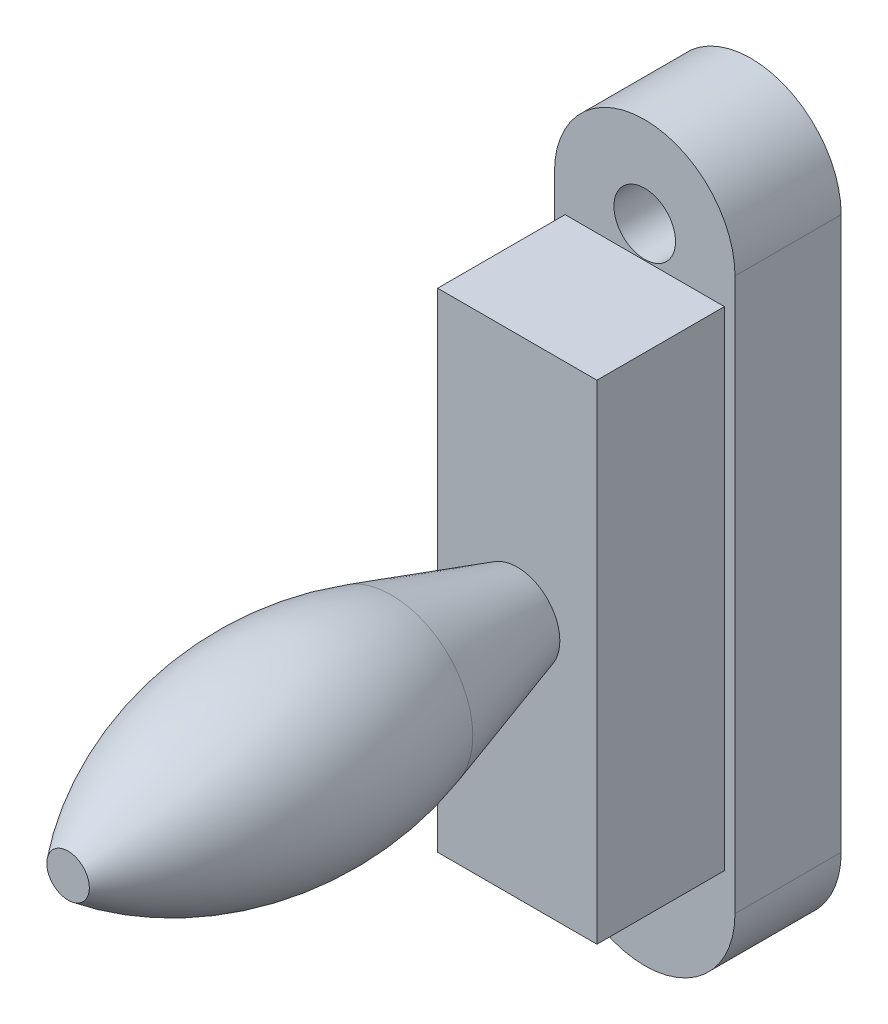
SolidWorks part; units mm, degrees
ref_plane "Front" through (0, 0, 0) normal (0, 0, 1) x (1, 0, 0)
ref_plane "Top" through (0, 0, 0) normal (0, 1, 0) x (1, 0, 0)
ref_plane "Right" through (0, 0, 0) normal (1, 0, 0) x (0, 0, -1)
sketch "Sketch1" plane through (0, 0, 0) normal (0, 0, 1) x (1, 0, 0)
  line L0 (0, 0) -> (0, 26) construction
  line L1 (-4.25, 0) -> (-4.25, 26)
  line L2 (4.25, 0) -> (4.25, 26)
  line L4 (-2.25, 3) -> (2.25, 3)
  line L5 (-2.25, 3) -> (-2.25, 23)
  line L6 (-2.25, 23) -> (2.25, 23)
  line L7 (2.25, 3) -> (2.25, 23)
  arc A0 (-4.25, 0) -> (4.25, 0) centre (0, 0) ccw
  arc A1 (4.25, 26) -> (-4.25, 26) centre (0, 26) ccw
  circle A2 centre (0, 26) radius 1.45
  circle A3 centre (0, 0) radius 1.45
  point P3 (0, 13)
  point P12 (0, 23)
  point P17 (4.25, 13)
  point P21 (2.25, 13)
  dimension "D1" = 2.9
  dimension "D2" = 26
  dimension "D3" = 4.5
  dimension "D4" = 2
  dimension "D5" = 20
extrude "Boss-Extrude1" add sketch "Sketch1" along normal blind 5
sketch "Sketch2" plane through (0, 0, 5) normal (0, 0, 1) x (1, 0, 0)
  line L0 (2.25, 23) -> (-2.25, 23) construction
  line L1 (2.25, 23) -> (-2.25, 23)
  line L2 (-2.25, 3) -> (2.25, 3) construction
  line L3 (2.25, 3) -> (2.25, 23) construction
  line L4 (-2.25, 23) -> (-2.25, 3) construction
  line L5 (-2.25, 3) -> (2.25, 3)
  line L6 (2.25, 3) -> (2.25, 23)
  line L7 (-2.25, 23) -> (-2.25, 3)
  line L8 (3.75, 1.5) -> (3.75, 24.5)
  line L9 (3.75, 24.5) -> (-3.75, 24.5)
  line L10 (-3.75, 24.5) -> (-3.75, 1.5)
  line L11 (-3.75, 1.5) -> (3.75, 1.5)
  dimension "D1" = 1.5
extrude "Boss-Extrude2" add sketch "Sketch2" along normal blind 5
sketch "Sketch3" plane through (0, 0, 10) normal (0, 0, 1) x (1, 0, 0)
  line L1 (-3.75, 24.5) -> (3.75, 24.5)
  line L2 (-3.75, 24.5) -> (-3.75, 1.5)
  line L3 (-3.75, 1.5) -> (3.75, 1.5)
  line L4 (3.75, 24.5) -> (3.75, 1.5)
extrude "Boss-Extrude3" add sketch "Sketch3" along normal blind 1
sketch "Sketch4" plane through (0, 0, 11) normal (0, 0, 1) x (1, 0, 0)
  line L1 (-3.75, 1.5) -> (3.75, 1.5) construction
  line L2 (-3.75, 1.5) -> (-3.75, 24.5) construction
  line L3 (-3.75, 24.5) -> (3.75, 24.5) construction
  line L4 (3.75, 1.5) -> (3.75, 24.5) construction
  line L5 (-3.75, 1.5) -> (3.75, 24.5) construction
  line L6 (-3.75, 24.5) -> (3.75, 1.5) construction
  point P0 (0, 13)
ref_axis "Axis1" through (0, 13, 11) along (0, 0, 1)
ref_plane "Plane1" through (0, 0, 0) normal (1, 0, 0) x (0, 0, -1)
sketch "Sketch5" plane through (0, 0, 0) normal (1, 0, 0) x (0, 0, -1)
  line L0 (-11, 13) -> (-11, 15.0039)
  line L1 (-11, 24.5) -> (-11, 1.5) construction
  line L2 (-11, 15.0039) -> (-16.9245, 16.8293)
  line L3 (-32.1512, 14.0019) -> (-32.1512, 13)
  line L4 (-32.1512, 13) -> (-11, 13)
  arc A0 (-16.9245, 16.8293) -> (-32.1512, 14.0019) centre (-21.8388, 0.8799) ccw
revolve "Revolve1" add sketch "Sketch5" angle 360 about L4
sketch "Sketch6" plane through (0, 1.5, 0) normal (0, -1, 0) x (1, 0, 0)
  circle A0 centre (0, 7.1539) radius 1.25
  dimension "D1" = 2.5
extrude "Cut-Extrude1" cut sketch "Sketch6" against normal up to next
